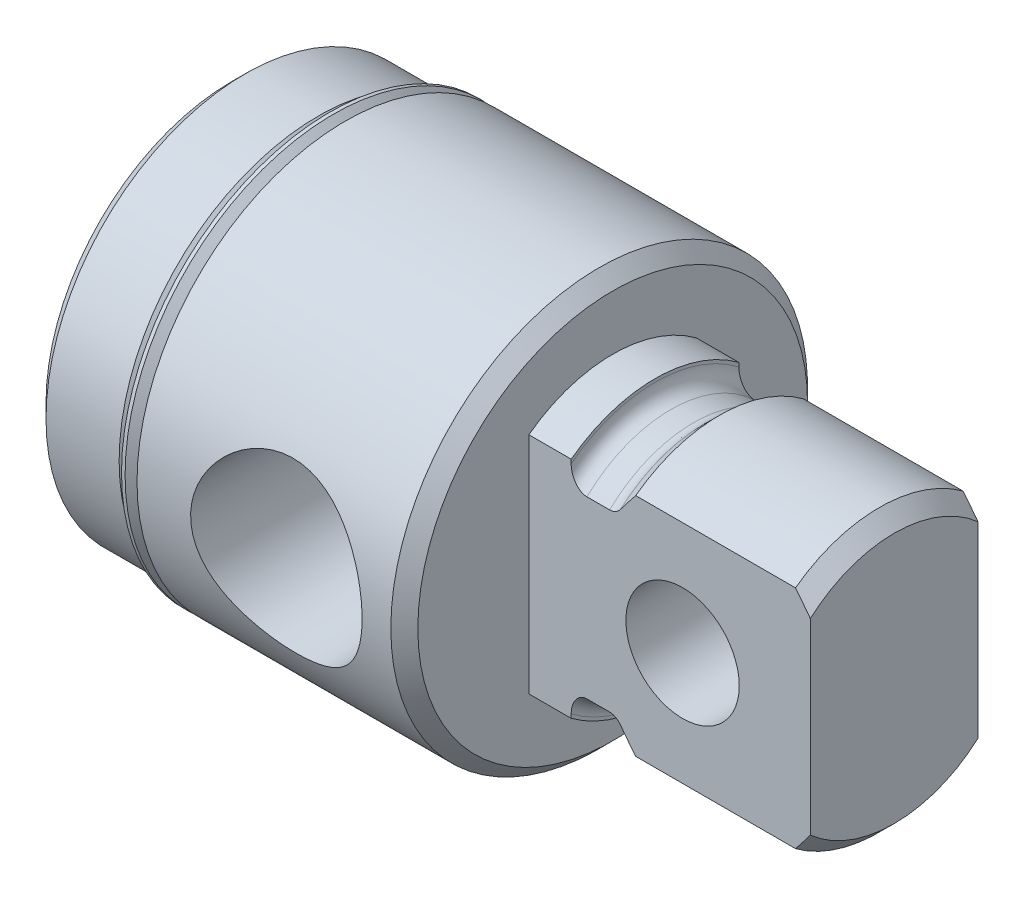
SolidWorks part; units mm, degrees
material "Cast Alloy Steel"
ref_plane "Front Plane" through (0, 0, 0) normal (0, 0, 1) x (1, 0, 0)
ref_plane "Top Plane" through (0, 0, 0) normal (0, 1, 0) x (1, 0, 0)
ref_plane "Right Plane" through (0, 0, 0) normal (1, 0, 0) x (0, 0, -1)
ref_plane "Plane1" through (37.3888, 0, 0) normal (1, 0, 0) x (0, 0, -1)
sketch "Sketch1" plane through (0, 0, 0) normal (0, 0, 1) x (1, 0, 0)
  line L0 (0, 0) -> (0, 10.4839)
  line L1 (0, 10.4839) -> (0.762, 11.2459)
  line L2 (0.762, 11.2459) -> (4.8895, 11.2459)
  line L3 (4.8895, 11.2459) -> (5.6515, 10.4839)
  line L4 (5.6515, 10.4839) -> (6.4135, 10.4839)
  line L5 (6.4135, 10.4839) -> (6.4135, 11.7602)
  line L6 (6.4135, 11.7602) -> (20.7391, 11.7602)
  line L7 (20.7391, 11.7602) -> (21.5011, 10.9982)
  line L8 (21.5011, 10.9982) -> (21.5011, 0)
  line L9 (21.5011, 0) -> (0, 0)
  line L10 (21.5011, 0) -> (0, 0) construction
revolve "Revolve1" add sketch "Sketch1" angle 360 about L10 reverse direction yes
sketch "Sketch2" plane through (0, 0, 0) normal (0, 0, 1) x (1, 0, 0)
  line L0 (21.5011, 0) -> (21.5011, 7.9057)
  line L1 (21.5011, 7.9057) -> (23.8887, 7.9057)
  line L2 (23.8887, 7.9057) -> (23.8887, 7.7279)
  line L3 (24.7777, 6.8389) -> (26.0604, 6.8389)
  line L4 (26.6591, 7.0708) -> (26.689, 7.098)
  line L5 (26.689, 7.098) -> (27.5285, 7.9375)
  line L6 (27.5285, 7.9375) -> (36.5493, 7.9375)
  line L7 (36.5493, 7.9375) -> (37.3888, 7.098)
  line L8 (37.3888, 7.098) -> (37.3888, 0)
  line L9 (37.3888, 0) -> (21.5011, 0)
  line L10 (37.3888, 0) -> (21.5011, 0) construction
  arc A0 (23.8887, 7.7279) -> (24.7777, 6.8389) centre (24.7777, 7.7279) ccw
  arc A1 (26.0604, 6.8389) -> (26.6591, 7.0708) centre (26.0604, 7.7279) ccw
revolve "Revolve2" add sketch "Sketch2" angle 360 about L10 reverse direction yes
cosmetic thread "Cosmetic Thread1" parameters "D1"=10.6998, "D2"=14.1961
sketch "Sketch3" plane through (37.3888, 0, 0) normal (1, 0, 0) x (0, 0, -1)
  line L0 (-23.5204, -47.0408) -> (23.5204, -47.0408)
  line L1 (23.5204, -47.0408) -> (23.5204, 47.0408)
  line L2 (23.5204, 47.0408) -> (-23.5204, 47.0408)
  line L3 (-23.5204, 47.0408) -> (-23.5204, -47.0408)
  line L4 (-4.7307, -23.5204) -> (4.7307, -23.5204)
  line L5 (4.7307, -23.5204) -> (4.7307, 23.5204)
  line L6 (4.7307, 23.5204) -> (-4.7307, 23.5204)
  line L7 (-4.7307, 23.5204) -> (-4.7307, -23.5204)
extrude "Cut-Extrude1" cut sketch "Sketch3" against normal blind 15.8877
ref_plane "Plane2" through (21.5011, 0, 0) normal (1, 0, 0) x (0, 0, -1)
hole_wizard "Hole1" positions "Sketch5" profile "Sketch4" legacy
sketch "Sketch5" plane through (0, 0, 0) normal (-1, 0, 0) x (0, 0, 1)
  point P0 (0, 0)
sketch "Sketch4" plane through (0, 0, 0) normal (0, 1, 0) x (0, 0, 1)
  line L0 (0, 0) -> (0, 20.9161)
  line L1 (0, 20.9161) -> (3.175, 19.083)
  line L2 (3.175, 19.083) -> (3.175, 0)
  line L4 (3.175, 0) -> (0, 0)
  line L6 (0, 20.9161) -> (-3.175, 19.083) construction
  line L7 (0, -4.2442) -> (0, 117.3081) construction
  dimension "Diameter" = 6.35
  dimension "Depth" = 19.083
  dimension "Drill Angle" = 120
ref_plane "Plane3" through (0, 0, 0) normal (0, 0.9998, 0.0175) x (1, 0, 0)
sketch "Sketch6" plane through (0, 0, 0) normal (0, 0.9998, 0.0175) x (1, 0, 0)
  line L0 (14.2748, 0) -> (18.8431, 0)
  line L1 (18.8431, 0) -> (18.8431, -3.0734)
  line L2 (18.8431, -3.0734) -> (19.1143, -11.7602)
  line L3 (19.1143, -11.7602) -> (14.2748, -11.7602)
  line L4 (14.2748, -11.7602) -> (14.2748, 0)
  line L5 (14.2748, -11.7602) -> (14.2748, 0) construction
revolve "Cut-Revolve1" cut sketch "Sketch6" angle 360 about L5 reverse direction yes
ref_plane "Plane4" through (14.2748, 0, 0) normal (1, 0, 0) x (0, 0, -1)
sketch "Sketch7" plane through (0, 0, 0) normal (0, 0, 1) x (1, 0, 0)
  line L0 (0, 0) -> (0, 6.4135)
  line L1 (0, 6.4135) -> (5.6642, 6.4135)
  line L2 (5.6642, 6.4135) -> (5.6642, 0)
  line L3 (5.6642, 0) -> (0, 0)
  line L4 (5.6642, 0) -> (0, 0) construction
revolve "Cut-Revolve2" cut sketch "Sketch7" angle 360 about L4 reverse direction yes
ref_plane "Plane5" through (5.6515, 0, 0) normal (1, 0, 0) x (0, 0, -1)
sketch "Sketch8" plane through (0, 0, 0) normal (0, 0, 1) x (1, 0, 0)
  line L0 (5.5369, 11.676) -> (6.291, 10.922)
  line L1 (6.291, 10.7424) -> (6.0325, 10.4838)
  line L2 (6.0325, 10.4838) -> (5.6515, 10.4838)
  line L3 (5.6515, 10.4838) -> (5.6515, 10.2298)
  line L4 (5.6515, 10.2298) -> (6.4135, 10.2298)
  line L5 (6.4135, 10.2298) -> (6.4135, 11.0868)
  line L6 (6.4135, 11.0868) -> (5.7401, 11.7602)
  line L7 (5.7401, 11.7602) -> (5.5369, 11.7602)
  line L8 (5.5369, 11.7602) -> (5.5369, 11.676)
  line L9 (6.4135, 0) -> (5.6515, 0) construction
  arc A0 (6.291, 10.922) -> (6.291, 10.7424) centre (6.2012, 10.8322) cw
revolve "Revolve3" add sketch "Sketch8" angle 360 about L9 reverse direction yes
ref_plane "Plane6" through (37.5158, 0, 0) normal (1, 0, 0) x (0, 0, -1)
sketch "Sketch9" plane through (0, 0, 0) normal (0, 0, 1) x (1, 0, 0)
  circle A0 centre (30.1752, 0) radius 3.2004
extrude "Cut-Extrude2" cut sketch "Sketch9" along normal blind 7.0961 and the other way blind 7.0961
ref_plane "Plane7" through (23.8887, 0, 0) normal (1, 0, 0) x (0, 0, -1)
ref_plane "Plane8" through (32.7406, 0, 0) normal (1, 0, 0) x (0, 0, -1)
ref_plane "Plane9" through (30.1752, 0, 0) normal (1, 0, 0) x (0, 0, -1)
ref_plane "Plane10" through (37.3888, 0, 0) normal (1, 0, 0) x (0, 0, -1)
ref_plane "Plane11" through (0, 0, 0) normal (0, 0, 1) x (1, 0, 0)
ref_plane "Plane12" through (23.8887, 0, 0) normal (1, 0, 0) x (0, 0, -1)
ref_plane "Plane13" through (0, 0, 0) normal (0, 1, 0) x (1, 0, 0)
ref_plane "Plane14" through (0, 0, 0) normal (0, 1, 0) x (1, 0, 0)
ref_plane "Plane15" through (21.5011, 0, 0) normal (1, 0, 0) x (0, 0, -1)
ref_plane "1 XY" through (23.8887, 0, 0) normal (1, 0, 0) x (0, 0, -1)
ref_plane "1 XZ" through (0, 0, 0) normal (0, -1, 0) x (-1, 0, 0)
ref_plane "1 YZ" through (0, 0, 0) normal (0, 0, -1) x (-1, 0, 0)
ref_axis "1 X" through (23.8887, 0, 80.9) along (0, 0, -1)
ref_axis "1 Y" through (23.8887, -50, 0) along (0, 1, 0)
ref_axis "1 Z" through (80.9, 0, 0) along (-1, 0, 0)
sketch3d "1"
  point P0 (23.8887, 0, 0)
ref_plane "c1 XY" through (0, 0, 0) normal (0, 0, 1) x (1, 0, 0)
ref_plane "c1 XZ" through (0, 7.9057, 0) normal (0, -1, 0) x (-1, 0, 0)
ref_plane "c1 YZ" through (21.5011, 0, 0) normal (1, 0, 0) x (0, 0, -1)
ref_axis "c1 X" through (-80.9, 7.9057, 0) along (1, 0, 0)
ref_axis "c1 Y" through (21.5011, -50, 0) along (0, 1, 0)
ref_axis "c1 Z" through (21.5011, 7.9057, 80.9) along (0, 0, -1)
sketch3d "c1"
  point P0 (21.5011, 7.9057, 0)
ref_plane "c2 XY" through (0, 0, 0) normal (0, 0, 1) x (1, 0, 0)
ref_plane "c2 XZ" through (0, -7.9057, 0) normal (0, -1, 0) x (-1, 0, 0)
ref_plane "c2 YZ" through (21.5011, 0, 0) normal (1, 0, 0) x (0, 0, -1)
ref_axis "c2 X" through (-80.9, -7.9057, 0) along (1, 0, 0)
ref_axis "c2 Y" through (21.5011, -50, 0) along (0, 1, 0)
ref_axis "c2 Z" through (21.5011, -7.9057, 80.9) along (0, 0, -1)
sketch3d "c2"
  point P0 (21.5011, -7.9057, 0)
ref_plane "cc1 XY" through (0, 0, 0) normal (0, 0, 1) x (1, 0, 0)
ref_plane "cc1 XZ" through (0, 0, 0) normal (0, -1, 0) x (-1, 0, 0)
ref_plane "cc1 YZ" through (21.5011, 0, 0) normal (1, 0, 0) x (0, 0, -1)
ref_axis "cc1 X" through (-80.9, 0, 0) along (1, 0, 0)
ref_axis "cc1 Y" through (21.5011, -50, 0) along (0, 1, 0)
ref_axis "cc1 Z" through (21.5011, 0, 80.9) along (0, 0, -1)
sketch3d "cc1"
  point P0 (21.5011, 0, 0)
ref_plane "cc2 XY" through (0, 0, 0) normal (0, 0, 1) x (1, 0, 0)
ref_plane "cc2 XZ" through (0, 0, 0) normal (0, -1, 0) x (-1, 0, 0)
ref_plane "cc2 YZ" through (23.8887, 0, 0) normal (1, 0, 0) x (0, 0, -1)
ref_axis "cc2 X" through (-80.9, 0, 0) along (1, 0, 0)
ref_axis "cc2 Y" through (23.8887, -50, 0) along (0, 1, 0)
ref_axis "cc2 Z" through (23.8887, 0, 80.9) along (0, 0, -1)
sketch3d "cc2"
  point P0 (23.8887, 0, 0)
ref_plane "lovra1 XY" through (32.7406, 0, 0) normal (1, 0, 0) x (0, 0, -1)
ref_plane "lovra1 XZ" through (0, 0, 0) normal (0, -1, 0) x (-1, 0, 0)
ref_plane "lovra1 YZ" through (0, 0, 0) normal (0, 0, -1) x (-1, 0, 0)
ref_axis "lovra1 X" through (32.7406, 0, 80.9) along (0, 0, -1)
ref_axis "lovra1 Y" through (32.7406, -50, 0) along (0, 1, 0)
ref_axis "lovra1 Z" through (80.9, 0, 0) along (-1, 0, 0)
sketch3d "lovra1"
  point P0 (32.7406, 0, 0)
ref_plane "lovra2 XY" through (32.7406, 0, 0) normal (1, 0, 0) x (0, 0, -1)
ref_plane "lovra2 XZ" through (0, 7.874, 0) normal (0, -1, 0) x (-1, 0, 0)
ref_plane "lovra2 YZ" through (0, 0, 0) normal (0, 0, -1) x (-1, 0, 0)
ref_axis "lovra2 X" through (32.7406, 7.874, 80.9) along (0, 0, -1)
ref_axis "lovra2 Y" through (32.7406, -50, 0) along (0, 1, 0)
ref_axis "lovra2 Z" through (80.9, 7.874, 0) along (-1, 0, 0)
sketch3d "lovra2"
  point P0 (32.7406, 7.874, 0)
ref_plane "lovra21 XY" through (0, 0, 0) normal (1, 0, 0) x (0, 0, -1)
ref_plane "lovra21 XZ" through (0, 0, 0) normal (0, -1, 0) x (-1, 0, 0)
ref_plane "lovra21 YZ" through (0, 0, 5.2705) normal (0, 0, -1) x (-1, 0, 0)
ref_axis "lovra21 X" through (0, 0, 80.9) along (0, 0, -1)
ref_axis "lovra21 Y" through (0, -50, 5.2705) along (0, 1, 0)
ref_axis "lovra21 Z" through (80.9, 0, 5.2705) along (-1, 0, 0)
sketch3d "lovra21"
  point P0 (0, 0, 5.2705)
ref_plane "lovra22 XY" through (0, 0, 0) normal (1, 0, 0) x (0, 0, -1)
ref_plane "lovra22 XZ" through (0, 0, 0) normal (0, -1, 0) x (-1, 0, 0)
ref_plane "lovra22 YZ" through (0, 0, -5.2705) normal (0, 0, -1) x (-1, 0, 0)
ref_axis "lovra22 X" through (0, 0, 80.9) along (0, 0, -1)
ref_axis "lovra22 Y" through (0, -50, -5.2705) along (0, 1, 0)
ref_axis "lovra22 Z" through (80.9, 0, -5.2705) along (-1, 0, 0)
sketch3d "lovra22"
  point P0 (0, 0, -5.2705)
ref_plane "lovra3 XY" through (32.7406, 0, 0) normal (1, 0, 0) x (0, 0, -1)
ref_plane "lovra3 XZ" through (0, -7.874, 0) normal (0, -1, 0) x (-1, 0, 0)
ref_plane "lovra3 YZ" through (0, 0, 0) normal (0, 0, -1) x (-1, 0, 0)
ref_axis "lovra3 X" through (32.7406, -7.874, 80.9) along (0, 0, -1)
ref_axis "lovra3 Y" through (32.7406, -50, 0) along (0, 1, 0)
ref_axis "lovra3 Z" through (80.9, -7.874, 0) along (-1, 0, 0)
sketch3d "lovra3"
  point P0 (32.7406, -7.874, 0)
ref_plane "olen XY" through (30.1752, 0, 0) normal (1, 0, 0) x (0, 0, -1)
ref_plane "olen XZ" through (0, 0, 0) normal (0, -1, 0) x (-1, 0, 0)
ref_plane "olen YZ" through (0, 0, 0) normal (0, 0, -1) x (-1, 0, 0)
ref_axis "olen X" through (30.1752, 0, 80.9) along (0, 0, -1)
ref_axis "olen Y" through (30.1752, -50, 0) along (0, 1, 0)
ref_axis "olen Z" through (80.9, 0, 0) along (-1, 0, 0)
sketch3d "olen"
  point P0 (30.1752, 0, 0)
ref_plane "p1 XY" through (37.3888, 0, 0) normal (1, 0, 0) x (0, 0, -1)
ref_plane "p1 XZ" through (0, 0, 0) normal (0, -1, 0) x (-1, 0, 0)
ref_plane "p1 YZ" through (0, 0, 4.7307) normal (0, 0, -1) x (-1, 0, 0)
ref_axis "p1 X" through (37.3888, 0, 80.9) along (0, 0, -1)
ref_axis "p1 Y" through (37.3888, -50, 4.7307) along (0, 1, 0)
ref_axis "p1 Z" through (80.9, 0, 4.7307) along (-1, 0, 0)
sketch3d "p1"
  point P0 (37.3888, 0, 4.7307)
ref_plane "p2 XY" through (37.3888, 0, 0) normal (1, 0, 0) x (0, 0, -1)
ref_plane "p2 XZ" through (0, 0, 0) normal (0, -1, 0) x (-1, 0, 0)
ref_plane "p2 YZ" through (0, 0, -4.7307) normal (0, 0, -1) x (-1, 0, 0)
ref_axis "p2 X" through (37.3888, 0, 80.9) along (0, 0, -1)
ref_axis "p2 Y" through (37.3888, -50, -4.7307) along (0, 1, 0)
ref_axis "p2 Z" through (80.9, 0, -4.7307) along (-1, 0, 0)
sketch3d "p2"
  point P0 (37.3888, 0, -4.7307)
ref_plane "port XY" through (0, 0, 0) normal (0, 0, 1) x (1, 0, 0)
ref_plane "port XZ" through (0, 0, 0) normal (0, -1, 0) x (-1, 0, 0)
ref_plane "port YZ" through (14.2748, 0, 0) normal (1, 0, 0) x (0, 0, -1)
ref_axis "port X" through (-80.9, 0, 0) along (1, 0, 0)
ref_axis "port Y" through (14.2748, -50, 0) along (0, 1, 0)
ref_axis "port Z" through (14.2748, 0, 80.9) along (0, 0, -1)
sketch3d "port"
  point P0 (14.2748, 0, 0)
ref_plane "port2 XY" through (37.3888, 0, 0) normal (1, 0, 0) x (0, 0, -1)
ref_plane "port2 XZ" through (0, 0, 0) normal (0, -1, 0) x (-1, 0, 0)
ref_plane "port2 YZ" through (0, 0, 0) normal (0, 0, -1) x (-1, 0, 0)
ref_axis "port2 X" through (37.3888, 0, 80.9) along (0, 0, -1)
ref_axis "port2 Y" through (37.3888, -50, 0) along (0, 1, 0)
ref_axis "port2 Z" through (80.9, 0, 0) along (-1, 0, 0)
sketch3d "port2"
  point P0 (37.3888, 0, 0)
ref_plane "thd1 XY" through (37.3888, 0, 0) normal (1, 0, 0) x (0, 0, -1)
ref_plane "thd1 XZ" through (0, 0, 0) normal (0, -1, 0) x (-1, 0, 0)
ref_plane "thd1 YZ" through (0, 0, 7.9375) normal (0, 0, -1) x (-1, 0, 0)
ref_axis "thd1 X" through (37.3888, 0, 80.9) along (0, 0, -1)
ref_axis "thd1 Y" through (37.3888, -50, 7.9375) along (0, 1, 0)
ref_axis "thd1 Z" through (80.9, 0, 7.9375) along (-1, 0, 0)
sketch3d "thd1"
  point P0 (37.3888, 0, 7.9375)
ref_plane "thd2 XY" through (37.3888, 0, 0) normal (1, 0, 0) x (0, 0, -1)
ref_plane "thd2 XZ" through (0, 0, 0) normal (0, -1, 0) x (-1, 0, 0)
ref_plane "thd2 YZ" through (0, 0, -7.9375) normal (0, 0, -1) x (-1, 0, 0)
ref_axis "thd2 X" through (37.3888, 0, 80.9) along (0, 0, -1)
ref_axis "thd2 Y" through (37.3888, -50, -7.9375) along (0, 1, 0)
ref_axis "thd2 Z" through (80.9, 0, -7.9375) along (-1, 0, 0)
sketch3d "thd2"
  point P0 (37.3888, 0, -7.9375)
ref_plane "to_mounting_bracket XY" through (21.5011, 0, 0) normal (1, 0, 0) x (0, 0, -1)
ref_plane "to_mounting_bracket XZ" through (0, 0, 0) normal (0, -1, 0) x (-1, 0, 0)
ref_plane "to_mounting_bracket YZ" through (0, 0, 0) normal (0, 0, -1) x (-1, 0, 0)
ref_axis "to_mounting_bracket X" through (21.5011, 0, 80.9) along (0, 0, -1)
ref_axis "to_mounting_bracket Y" through (21.5011, -50, 0) along (0, 1, 0)
ref_axis "to_mounting_bracket Z" through (80.9, 0, 0) along (-1, 0, 0)
sketch3d "to_mounting_bracket"
  point P0 (21.5011, 0, 0)
ref_plane "to_nut XY" through (23.8887, 0, 0) normal (1, 0, 0) x (0, 0, -1)
ref_plane "to_nut XZ" through (0, 0, 0) normal (0, -1, 0) x (-1, 0, 0)
ref_plane "to_nut YZ" through (0, 0, 0) normal (0, 0, -1) x (-1, 0, 0)
ref_axis "to_nut X" through (23.8887, 0, 80.9) along (0, 0, -1)
ref_axis "to_nut Y" through (23.8887, -50, 0) along (0, 1, 0)
ref_axis "to_nut Z" through (80.9, 0, 0) along (-1, 0, 0)
sketch3d "to_nut"
  point P0 (23.8887, 0, 0)
ref_plane "to_pin XY" through (0, 0, 0) normal (0, 0, 1) x (1, 0, 0)
ref_plane "to_pin XZ" through (0, 0, 0) normal (0, -1, 0) x (-1, 0, 0)
ref_plane "to_pin YZ" through (30.1752, 0, 0) normal (1, 0, 0) x (0, 0, -1)
ref_axis "to_pin X" through (-80.9, 0, 0) along (1, 0, 0)
ref_axis "to_pin Y" through (30.1752, -50, 0) along (0, 1, 0)
ref_axis "to_pin Z" through (30.1752, 0, 80.9) along (0, 0, -1)
sketch3d "to_pin"
  point P0 (30.1752, 0, 0)
ref_plane "to_screw XY" through (0, 0, 0) normal (0, 1, 0) x (1, 0, 0)
ref_plane "to_screw XZ" through (0, 0, 0) normal (0, 0, 1) x (1, 0, 0)
ref_plane "to_screw YZ" through (14.2748, 0, 0) normal (1, 0, 0) x (0, 0, -1)
ref_axis "to_screw X" through (-80.9, 0, 0) along (1, 0, 0)
ref_axis "to_screw Y" through (14.2748, 0, 50) along (0, 0, -1)
ref_axis "to_screw Z" through (14.2748, 50, 0) along (0, -1, 0)
sketch3d "to_screw"
  point P0 (14.2748, 0, 0)
ref_plane "to_tube XY" through (5.6515, 0, 0) normal (1, 0, 0) x (0, 0, -1)
ref_plane "to_tube XZ" through (0, 0, 0) normal (0, -1, 0) x (-1, 0, 0)
ref_plane "to_tube YZ" through (0, 0, 0) normal (0, 0, -1) x (-1, 0, 0)
ref_axis "to_tube X" through (5.6515, 0, 80.9) along (0, 0, -1)
ref_axis "to_tube Y" through (5.6515, -50, 0) along (0, 1, 0)
ref_axis "to_tube Z" through (80.9, 0, 0) along (-1, 0, 0)
sketch3d "to_tube"
  point P0 (5.6515, 0, 0)
